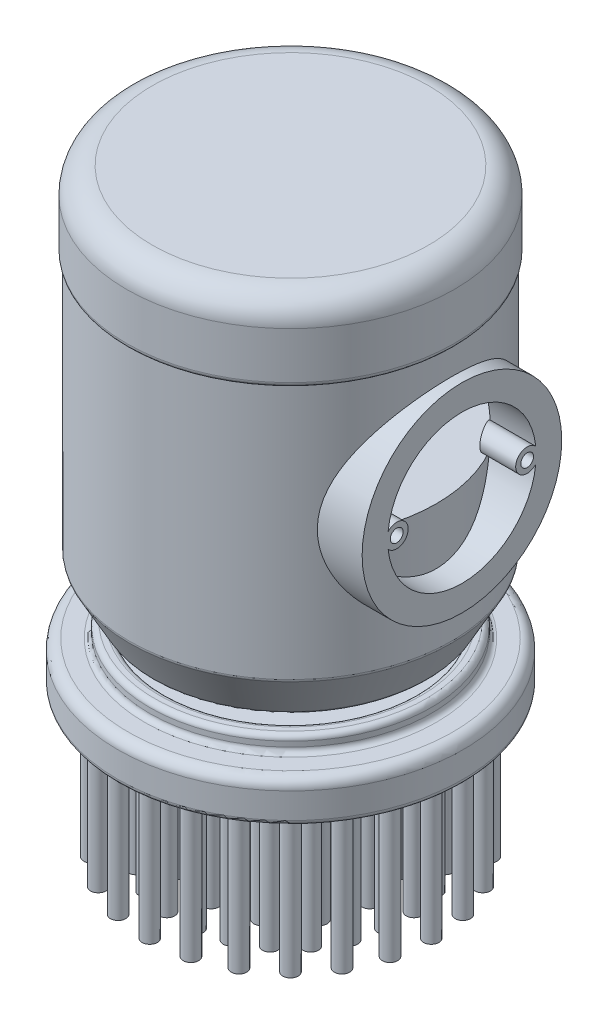
SolidWorks part; units mm, degrees
ref_plane "Front Plane" through (0, 0, 0) normal (0, 0, 1) x (1, 0, 0)
ref_plane "Top Plane" through (0, 0, 0) normal (0, 1, 0) x (1, 0, 0)
ref_plane "Right Plane" through (0, 0, 0) normal (1, 0, 0) x (0, 0, -1)
sketch "Sketch1" plane through (0, 0, 0) normal (0, 0, 1) x (1, 0, 0)
  line L0 (26.5, 0) -> (31.5, 9)
  line L1 (0, 0) -> (31.5, 0)
  line L2 (0, 0) -> (0, 74)
  line L3 (0, 74) -> (31.5, 74)
  line L4 (31.5, 0) -> (31.5, 74)
  line L6 (0, 0) -> (1.5, 0)
  line L7 (0, 0) -> (0, -3)
  line L8 (0, -3) -> (1.5, -3)
  line L9 (1.5, 0) -> (1.5, -3)
  line L10 (0, -3) -> (27.5, -3)
  line L11 (0, -3) -> (0, -6)
  line L12 (0, -6) -> (27.5, -6)
  line L13 (27.5, -3) -> (27.5, -6)
  line L14 (0, -6) -> (33.75, -6)
  line L15 (0, -6) -> (0, -14)
  line L16 (0, -14) -> (33.75, -14)
  line L17 (33.75, -6) -> (33.75, -14)
  dimension "D1" = 31.5
  dimension "D2" = 26.5
  dimension "D3" = 74
  dimension "D4" = 9
  dimension "D5" = 3
  dimension "D6" = 1.5
  dimension "D7" = 27.5
  dimension "D8" = 3
  dimension "D9" = 33.75
  dimension "D10" = 8
revolve "Revolve1" add sketch "Sketch1" angle 360 about L2 region at (15.6127, 37.3314, 0) region at (0.75, -1.5, 0) region at (13.75, -4.5, 0) region at (16.875, -10, 0)
sketch "Sketch2" plane through (0, -3, 0) normal (0, 1, 0) x (1, 0, 0)
  circle A0 centre (0, 0) radius 24.5
  circle A2 centre (0, 0) radius 13
  circle A3 centre (0, 0) radius 27.5 construction
  dimension "D1" = 3
  dimension "D2" = 26
extrude "Cut-Extrude2" cut sketch "Sketch2" against normal blind 2
sketch "Sketch5" plane through (0, 0, 0) normal (1, 0, 0) x (0, 0, -1)
  line L1 (31.5, 74) -> (-31.5, 74) construction
  circle A0 centre (0, 34.5) radius 19.5
  point P4 (0, 0)
  dimension "D1" = 39
  dimension "D2" = 39.5
extrude "Boss-Extrude3" add sketch "Sketch5" along normal blind 33.5
sketch "Sketch7" plane through (0, 74, 0) normal (0, 1, 0) x (1, 0, 0)
  circle A0 centre (0, 0) radius 28.5
  circle A1 centre (0, 0) radius 31.5 construction
  dimension "D1" = 3
extrude "Cut-Extrude3" cut sketch "Sketch7" against normal blind 43
sketch "Sketch3" plane through (0, 74, 0) normal (0, 1, 0) x (1, 0, 0)
  circle A0 centre (0, 0) radius 32
  dimension "D1" = 64
extrude "Boss-Extrude1" add sketch "Sketch3" against normal blind 15
sketch "Sketch4" plane through (0, -14, 0) normal (0, -1, 0) x (1, 0, 0)
  line L0 (0, 27.5) -> (0, 0) construction
  line L1 (0, 0) -> (7.1175, 26.563) construction
  line L2 (3.5895, 27.2647) -> (0, 0) construction
  line L3 (0, 21.6855) -> (2.8063, 21.3161)
  line L4 (2.8063, 21.3161) -> (5.6126, 20.9466)
  line L5 (0, 0) -> (2.8063, 21.3161) construction
  line L6 (0, 0) -> (8.2277, 19.8634) construction
  circle A0 centre (0, 0) radius 27.5 construction
  circle A1 centre (0, 27.5) radius 1.5
  circle A2 centre (0, 0) radius 21.5 construction
  circle A3 centre (0, 0) radius 15.5 construction
  circle A4 centre (0, 15.5) radius 1.5
  circle A5 centre (7.1175, 26.563) radius 1.5
  circle A6 centre (13.75, 23.8157) radius 1.5
  circle A7 centre (19.4454, 19.4454) radius 1.5
  circle A8 centre (23.8157, 13.75) radius 1.5
  circle A9 centre (26.563, 7.1175) radius 1.5
  circle A10 centre (27.5, 0) radius 1.5
  circle A11 centre (26.563, -7.1175) radius 1.5
  circle A12 centre (23.8157, -13.75) radius 1.5
  circle A13 centre (19.4454, -19.4454) radius 1.5
  circle A14 centre (13.75, -23.8157) radius 1.5
  circle A15 centre (7.1175, -26.563) radius 1.5
  circle A16 centre (0, -27.5) radius 1.5
  circle A17 centre (-7.1175, -26.563) radius 1.5
  circle A18 centre (-13.75, -23.8157) radius 1.5
  circle A19 centre (-19.4454, -19.4454) radius 1.5
  circle A20 centre (-23.8157, -13.75) radius 1.5
  circle A21 centre (-26.563, -7.1175) radius 1.5
  circle A22 centre (-27.5, 0) radius 1.5
  circle A23 centre (-26.563, 7.1175) radius 1.5
  circle A24 centre (-23.8157, 13.75) radius 1.5
  circle A25 centre (-19.4454, 19.4454) radius 1.5
  circle A26 centre (2.8063, 21.3161) radius 1.5
  circle A27 centre (0, 0) radius 9.5 construction
  circle A28 centre (-13.75, 23.8157) radius 1.5
  circle A29 centre (-7.1175, 26.563) radius 1.5
  circle A30 centre (8.2277, 19.8634) radius 1.5
  circle A31 centre (13.0884, 17.0571) radius 1.5
  circle A32 centre (17.0571, 13.0884) radius 1.5
  circle A33 centre (19.8634, 8.2277) radius 1.5
  circle A34 centre (21.3161, 2.8063) radius 1.5
  circle A35 centre (21.3161, -2.8063) radius 1.5
  circle A36 centre (19.8634, -8.2277) radius 1.5
  circle A37 centre (17.0571, -13.0884) radius 1.5
  circle A38 centre (13.0884, -17.0571) radius 1.5
  circle A39 centre (8.2277, -19.8634) radius 1.5
  circle A40 centre (2.8063, -21.3161) radius 1.5
  circle A41 centre (-2.8063, -21.3161) radius 1.5
  circle A42 centre (-8.2277, -19.8634) radius 1.5
  circle A43 centre (-13.0884, -17.0571) radius 1.5
  circle A44 centre (-17.0571, -13.0884) radius 1.5
  circle A45 centre (-19.8634, -8.2277) radius 1.5
  circle A46 centre (-21.3161, -2.8063) radius 1.5
  circle A47 centre (-21.3161, 2.8063) radius 1.5
  circle A48 centre (-19.8634, 8.2277) radius 1.5
  circle A49 centre (-17.0571, 13.0884) radius 1.5
  circle A50 centre (-13.0884, 17.0571) radius 1.5
  circle A51 centre (-8.2277, 19.8634) radius 1.5
  circle A52 centre (-2.8063, 21.3161) radius 1.5
  circle A53 centre (4.0117, 14.9719) radius 1.5
  circle A54 centre (7.75, 13.4234) radius 1.5
  circle A55 centre (10.9602, 10.9602) radius 1.5
  circle A56 centre (13.4234, 7.75) radius 1.5
  circle A57 centre (14.9719, 4.0117) radius 1.5
  circle A58 centre (15.5, 0) radius 1.5
  circle A59 centre (14.9719, -4.0117) radius 1.5
  circle A60 centre (13.4234, -7.75) radius 1.5
  circle A61 centre (10.9602, -10.9602) radius 1.5
  circle A62 centre (7.75, -13.4234) radius 1.5
  circle A63 centre (4.0117, -14.9719) radius 1.5
  circle A64 centre (0, -15.5) radius 1.5
  circle A65 centre (-4.0117, -14.9719) radius 1.5
  circle A66 centre (-7.75, -13.4234) radius 1.5
  circle A67 centre (-10.9602, -10.9602) radius 1.5
  circle A68 centre (-13.4234, -7.75) radius 1.5
  circle A69 centre (-14.9719, -4.0117) radius 1.5
  circle A70 centre (-15.5, 0) radius 1.5
  circle A71 centre (-14.9719, 4.0117) radius 1.5
  circle A72 centre (-13.4234, 7.75) radius 1.5
  circle A73 centre (-10.9602, 10.9602) radius 1.5
  circle A74 centre (-7.75, 13.4234) radius 1.5
  circle A75 centre (-4.0117, 14.9719) radius 1.5
  point P54 (0, 0)
  point P159 (0, 0)
  dimension "D1" = 6
  dimension "60" = 55
  dimension "D2" = 3
  dimension "D3" = 6
  dimension "D4" = 3
  dimension "D6" = 3
  dimension "D7" = 6
  dimension "D9" = 15
  dimension "D5" = 24
  dimension "D8" = 24
  dimension "D10" = 24
extrude "Boss-Extrude2" add sketch "Sketch4" along normal blind 29 contours A10 | A9 | A8 | A7 | A6 | A5 | A1 | A29 | A28 | A25 | A24 | A23 | A22 | A21 | A20 | A19 | A18 | A16 | A15 | A14 | A13 | A12 | A11 | A52 | A51 | A50 | A49 | A48 | A47 | A46 | A45 | A44 | A43 | A42 | A41 | A40 | A39 | A37 | A35 | A34 | A33 | A30 | L4 A26 L3 | L3 A26 L4 | A4 | A53 | A54 | A55 | A56 | A57 | A58 | A59 | A60 | A61 | A63 | A64 | A65 | A66 | A67 | A68 | A69 | A70 | A75 | A74 | A73 | A72 | A71 | A17 | A38 | A36 | A32 | A31 | A62 region at (2.8894, -14, 21.9472) region at (2.7232, -14, 20.6849) region at (0, -14, 27.5) region at (0, -14, 15.5) region at (7.1175, -14, 26.563) region at (13.75, -14, 23.8157) region at (19.4454, -14, 19.4454) region at (23.8157, -14, 13.75) region at (26.563, -14, 7.1175) region at (27.5, -14, 0) region at (26.563, -14, -7.1175) region at (23.8157, -14, -13.75) region at (19.4454, -14, -19.4454) region at (13.75, -14, -23.8157) region at (7.1175, -14, -26.563) region at (0, -14, -27.5) region at (-13.75, -14, -23.8157) region at (-19.4454, -14, -19.4454) region at (-23.8157, -14, -13.75) region at (-26.563, -14, -7.1175) region at (-27.5, -14, 0) region at (-26.563, -14, 7.1175) region at (-23.8157, -14, 13.75) region at (-19.4454, -14, 19.4454) region at (-13.75, -14, 23.8157) region at (-7.1175, -14, 26.563) region at (8.2277, -14, 19.8634) region at (19.8634, -14, 8.2277) region at (21.3161, -14, 2.8063) region at (21.3161, -14, -2.8063) region at (17.0571, -14, -13.0884) region at (8.2277, -14, -19.8634) region at (2.8063, -14, -21.3161) region at (-2.8063, -14, -21.3161) region at (-8.2277, -14, -19.8634) region at (-13.0884, -14, -17.0571) region at (-17.0571, -14, -13.0884) region at (-19.8634, -14, -8.2277) region at (-21.3161, -14, -2.8063) region at (-21.3161, -14, 2.8063) region at (-19.8634, -14, 8.2277) region at (-17.0571, -14, 13.0884) region at (-13.0884, -14, 17.0571) region at (-8.2277, -14, 19.8634) region at (-2.8063, -14, 21.3161) region at (4.0117, -14, 14.9719) region at (7.75, -14, 13.4234) region at (10.9602, -14, 10.9602) region at (13.4234, -14, 7.75) region at (14.9719, -14, 4.0117) region at (15.5, -14, 0) region at (14.9719, -14, -4.0117) region at (13.4234, -14, -7.75) region at (10.9602, -14, -10.9602) region at (4.0117, -14, -14.9719) region at (0, -14, -15.5) region at (-4.0117, -14, -14.9719) region at (-7.75, -14, -13.4234) region at (-10.9602, -14, -10.9602) region at (-13.4234, -14, -7.75)
fillet "Fillet1" radius 5 1 edges at (0, 74, 32)
fillet "Fillet2" radius 1 7 edges at (0, -3, 24.5) (0, -3, -27.5) (0, -14, -33.75) (0, -6, -27.5) (0, 0, -26.5) (0, 9, -31.5) (0, 59, 32)
fillet "Fillet3" radius 2 1 edges at (0, -6, -33.75)
sketch "Sketch6" plane through (33.5, 0, 0) normal (1, 0, 0) x (0, 0, -1)
  circle A0 centre (0, 34.5) radius 14.5
  circle A1 centre (0, 34.5) radius 19.5 construction
  dimension "D1" = 5
extrude "Cut-Extrude4" cut sketch "Sketch6" against normal up to surface (8.9643 mm away) up to face at (0, 31, 28.5)
sketch "Sketch9" plane through (0, 0, 0) normal (0, 0, 1) x (1, 0, 0)
  line L0 (33.5, 34.5) -> (24.7386, 34.5) construction
  line L1 (33.5, 15) -> (33.5, 54) construction
  spline S0 degree 2 poles (31.5, 15) (19.4286, 34.5) (31.5, 54) knots 0 0 0 1 1 1 weights 0.012 0.0315 0.051 construction
sketch "Sketch10" plane through (33.5, 0, 0) normal (1, 0, 0) x (0, 0, -1)
  line L0 (-19.5, 34.5) -> (19.5, 34.5) construction
  line L1 (0, 54) -> (0, 15) construction
  circle A0 centre (-12.75, 34.5) radius 2.25
  circle A1 centre (-12.75, 34.5) radius 1.25
  circle A2 centre (0, 34.5) radius 19.5 construction
  circle A5 centre (-12.75, 34.5) radius 1.75 construction
  circle A6 centre (0, 34.5) radius 14.5 construction
  circle A7 centre (12.75, 34.5) radius 2.25
  circle A8 centre (12.75, 34.5) radius 1.25
  dimension "D1" = 2.5
  dimension "D2" = 1
  dimension "D3" = 0.5
extrude "Boss-Extrude5" add sketch "Sketch10" against normal up to surface (7.0047 mm away) up to face at (-0.0136, 39.9732, 0.6225)
